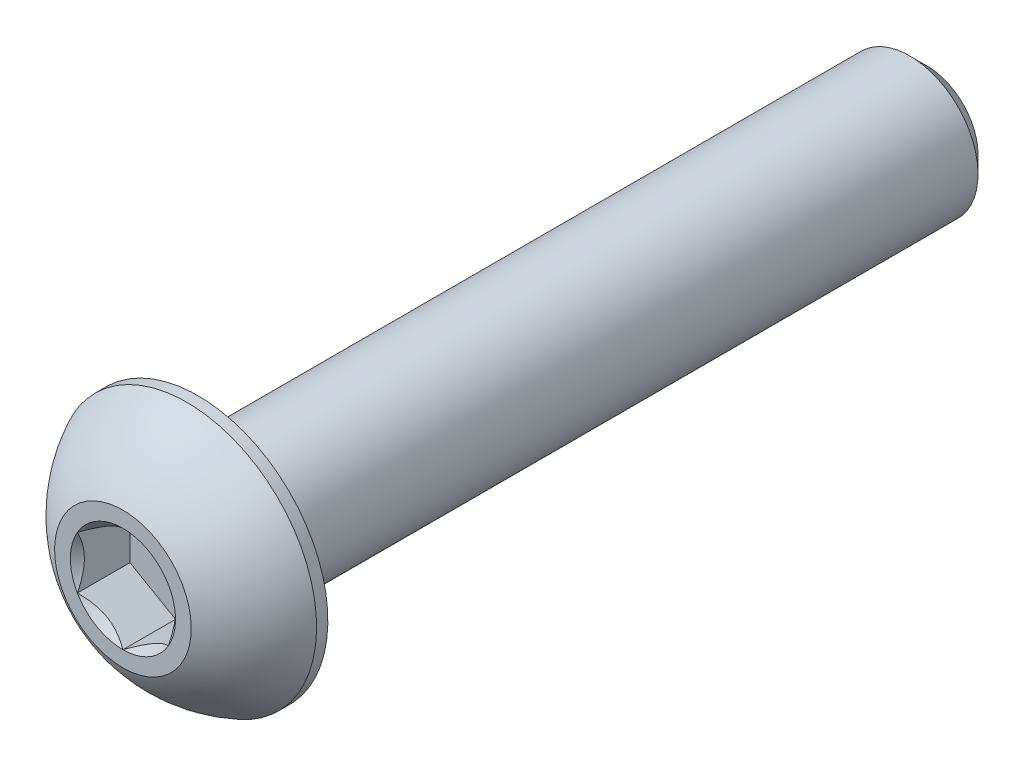
SolidWorks part; units mm, degrees
ref_plane "Front" through (0, 0, 0) normal (0, 0, 1) x (1, 0, 0)
ref_plane "Top" through (0, 0, 0) normal (0, 1, 0) x (1, 0, 0)
ref_plane "Right" through (0, 0, 0) normal (1, 0, 0) x (0, 0, -1)
sketch "Sketch1" plane through (0, 0, 0) normal (1, 0, 0) x (0, 0, -1)
  line L2 (-8, 1.5) -> (8, 1.5)
  line L3 (8, 1.5) -> (8, 0)
  line L4 (8, 0) -> (-8, 0)
  line L6 (-8.2475, 2.85) -> (-8, 2.85) construction
  line L7 (8, 1.5) -> (8, -1.5) construction
  line L8 (-9.65, 0) -> (-8, 0) construction
  line L9 (-8, 2.85) -> (-8, -2.85) construction
  line L11 (-8, 1.5) -> (-8, 0)
  line L13 (-9.65, 1) -> (-9.65, -1) construction
  line L14 (-9.65, 1) -> (-9.65, 1.5) construction
  line L15 (7.9688, 1.5541) -> (8.2188, 1.1211) construction
  line L16 (8.2188, 1.1211) -> (8.4688, 1.5541) construction
  line L17 (8.4688, 1.5541) -> (7.9688, 1.5541) construction
  line L18 (8, 1.5) -> (8.4375, 1.5) construction
  line L19 (8.2188, 1.5541) -> (8.2188, 1.5) construction
  line L20 (8.2188, 1.5) -> (8.2188, 1.1752) construction
  line L21 (8.2188, 1.1752) -> (8.2188, 1.1211) construction
  line L22 (8.1875, 1.1752) -> (8.25, 1.1752)
  line L23 (7.9844, 1.5271) -> (8.4531, 1.5271)
  line L24 (8.25, 1.1752) -> (8.4531, 1.5271)
  line L25 (8.1875, 1.1752) -> (7.9844, 1.5271)
  line L26 (7.625, 1.5) -> (8, 1.125)
  arc A3 (-9.65, 1.5) -> (-8.2475, 2.85) centre (-6.8552, 0) cw construction
  point P29 (8.2188, 1.5271)
  point P30 (6.75, -1.5)
  point P33 (0, 0)
  dimension "Thread Size" = 3
  dimension "D1" = 0.2475
  dimension "Head Height" = 1.65
  dimension "Head Diameter" = 5.7
  dimension "Length" = 16
  dimension "Drive Size" = 2
  dimension "Thread Pitch" = 0.5
  dimension "D3" = 0.0625
  dimension "D2" = 0.375
  dimension "D4" = 45
  dimension "D5" = 1.25
sketch "Sketch10" plane through (0, 0, 0) normal (1, 0, 0) x (0, 0, -1)
  line L0 (7.625, 1.5) -> (8, 1.125) construction
  line L1 (7.625, 1.5) -> (8, 1.125)
  line L4 (8, 1.5) -> (-8, 1.5)
  line L5 (8, 0) -> (8, 1.5)
  line L6 (-8, 0) -> (8, 0)
  line L7 (-8, 1.5) -> (-8, 0)
  line L8 (7.625, 1.5) -> (-8, 1.5)
  line L9 (8, 0) -> (8, 1.125)
  line L10 (-8, 0) -> (8, 0)
  line L11 (-8, 1.5) -> (-8, 0)
  dimension "D1" = 0
revolve "Revolve3" add sketch "Sketch10" angle 360 about L8
sketch "Sketch7" plane through (0, 0, 0) normal (1, 0, 0) x (0, 0, -1)
  line L6 (-8.2475, 2.85) -> (-8, 2.85) construction
  line L8 (-9.65, 0) -> (-8, 0) construction
  line L11 (-8, 2.85) -> (-8, -2.85) construction
  line L12 (-8.2475, 2.85) -> (-8, 2.85)
  line L13 (-9.65, 0) -> (-8, 0)
  line L14 (-9.65, 1) -> (-9.65, -1) construction
  line L15 (-8, 2.85) -> (-8, 0)
  line L16 (-9.65, 1.5) -> (-9.65, 0)
  arc A2 (-8.2475, 2.85) -> (-9.65, 1.5) centre (-6.8552, 0) ccw construction
  arc A3 (-8.2475, 2.85) -> (-9.65, 1.5) centre (-6.8552, 0) ccw
revolve "Revolve2" add sketch "Sketch7" angle 360 mid plane about L13
sketch "Sketch5" plane through (0, 0, 9.65) normal (0, 0, 1) x (1, 0, 0)
  line L1 (1, -0.5774) -> (1, 0.5774)
  line L2 (1, 0.5774) -> (0, 1.1547)
  line L3 (0, 1.1547) -> (-1, 0.5774)
  line L4 (-1, 0.5774) -> (-1, -0.5774)
  line L5 (-1, -0.5774) -> (0, -1.1547)
  line L6 (0, -1.1547) -> (1, -0.5774)
  circle A0 centre (0, 0) radius 1 construction
extrude "Cut-Extrude2" cut sketch "Sketch5" against normal blind 1.155
sketch "Sketch6" plane through (0, 0, 9.65) normal (0, 0, 1) x (1, 0, 0)
  circle A0 centre (0, 0) radius 1.1547
extrude "Cut-Extrude3" cut sketch "Sketch6" against normal blind 1.155 draft 45
sketch "Sketch9" plane through (0, 0, 8) normal (0, 0, -1) x (-1, 0, 0)
  circle A0 centre (0, 0) radius 1.5 construction
  circle A4 centre (0, 0) radius 1.5
split "Split1" [suppressed] bodies to split 113
sketch "Sketch11" plane through (0, 0, -8) normal (0, 0, -1) x (-1, 0, 0)
  circle A0 centre (0, 0) radius 1.5 construction
  circle A1 centre (0, 0) radius 1.5
curve "Helix/Spiral1" [suppressed] pitch 0.5 height 17.65 turns 35.3
sketch "Sketch12" plane through (0, 0, 0) normal (1, 0, 0) x (0, 0, -1)
  line L0 (8.1875, 1.1752) -> (8.25, 1.1752) construction
  line L1 (8.25, 1.1752) -> (8.4531, 1.5271) construction
  line L2 (7.9844, 1.5271) -> (8.4531, 1.5271) construction
  line L3 (8.1875, 1.1752) -> (7.9844, 1.5271) construction
  line L4 (8.1875, 1.1752) -> (8.25, 1.1752)
  line L5 (8.25, 1.1752) -> (8.4531, 1.5271)
  line L6 (7.9844, 1.5271) -> (8.4531, 1.5271)
  line L7 (8.1875, 1.1752) -> (7.9844, 1.5271)
sweep "Cut-Sweep2" [suppressed] cut profiles "Sketch12" path "Helix/Spiral1"
extrude "Boss-Extrude1" [suppressed] add sketch "Sketch9" along normal blind 10 draft 45
equation "\"D1@Cut-Extrude2\" = \"Head Height@Sketch1\" * .7"
equation "\"D1@Sketch1\" = \"Head Height@Sketch1\" * .15"
equation "\"D1@Cut-Extrude3\" = \"D1@Cut-Extrude2\""
equation "\"D3@Sketch1\" = \"Thread Pitch@Sketch1\" / 8"
equation "\"D2@Sketch1\" = \"Thread Pitch@Sketch1\" * 0.75"
equation "\"D3@Helix/Spiral1\" = \"Length@Sketch1\" + \"Head Height@Sketch1\""
equation "\"D4@Helix/Spiral1\" = \"Thread Pitch@Sketch1\""
equation "\"D5@Sketch1\" = \"Thread Pitch@Sketch1\" * 2.5"
